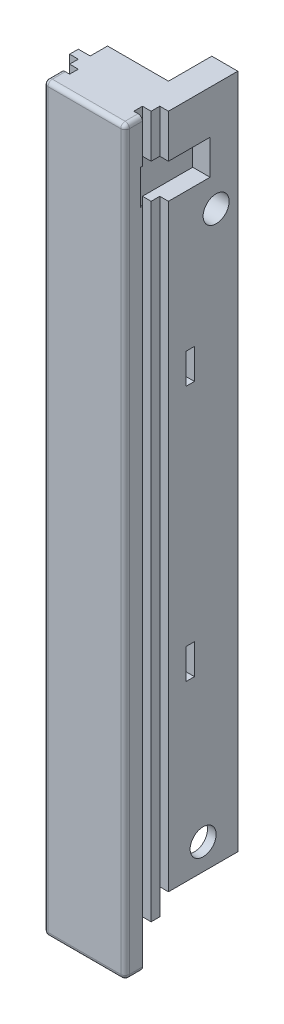
SolidWorks part; units mm, degrees
ref_plane "Front Plane" through (0, 0, 0) normal (0, 0, 1) x (1, 0, 0)
ref_plane "Top Plane" through (0, 0, 0) normal (0, 1, 0) x (1, 0, 0)
ref_plane "Right Plane" through (0, 0, 0) normal (1, 0, 0) x (0, 0, -1)
sketch "Sketch1" plane through (0, 0, 0) normal (0, 1, 0) x (1, 0, 0)
  line L0 (-3.4214, 1.8186) -> (-3.4214, 0.8186)
  line L1 (-4.4214, 3.8186) -> (4.9786, 3.8186)
  line L2 (-4.4214, 3.8186) -> (-4.4214, 1.8186)
  line L3 (-4.4214, 1.8186) -> (4.9786, 1.8186)
  line L4 (4.9786, 3.8186) -> (4.9786, 1.8186)
  line L5 (-3.4214, 0.8186) -> (-4.4214, 0.8186)
  line L6 (-4.4214, 0.8186) -> (-4.4214, -0.1814)
  line L7 (-4.4214, -0.1814) -> (4.9786, -0.1814)
  line L8 (4.9786, -0.1814) -> (4.9786, 0.8186)
  line L9 (4.9786, 0.8186) -> (3.9786, 0.8186)
  line L10 (3.9786, 0.8186) -> (3.9786, 1.8186)
  line L11 (4.9786, -0.1814) -> (5.9786, -0.1814)
  line L12 (5.9786, -0.1814) -> (5.9786, -8.1814)
  line L13 (5.9786, -8.1814) -> (2.9786, -8.1814)
  line L14 (2.9786, -8.1814) -> (2.9786, -3.1814)
  line L15 (2.9786, -3.1814) -> (-4.051, -3.1814)
  line L16 (-4.051, -3.1814) -> (-4.051, -1.1814)
  line L17 (-4.051, -1.1814) -> (-5.4214, -1.1814)
  line L18 (-5.4214, -1.1814) -> (-5.4214, -0.1814)
  line L19 (-5.4214, -0.1814) -> (-4.4214, -0.1814)
  dimension "D1" = 9.4
  dimension "D2" = 2
  dimension "D3" = 1
  dimension "D4" = 1
  dimension "D5" = 1
  dimension "D6" = 1
  dimension "D7" = 1
  dimension "D8" = 1
  dimension "D9" = 1
  dimension "D10" = 1
  dimension "D11" = 1
  dimension "D12" = 8
  dimension "D13" = 3
  dimension "D14" = 3
extrude "Boss-Extrude1" add sketch "Sketch1" against normal blind 85.5 contours L4 L1 L2 L3 region at (0.2786, 0, -2.8186)
extrude "Boss-Extrude2" add sketch "Sketch1<3>" against normal blind 81 contours L9 L10 L3 L0 L5 L6 L7 L8 region at (0.2786, 0, -0.7591)
sketch "Sketch1<3>" plane through (0, 0, 0) normal (0, 1, 0) x (1, 0, 0) same geometry as "Sketch1"
fillet "Fillet1" radius 0.5 8 edges at (-4.4214, -85.5, -2.8186) (4.9786, -85.5, -2.8186) (0.2786, -85.5, -3.8186) (-4.4214, 0, -2.8186) (4.9786, 0, -2.8186) (0.2786, 0, -3.8186) (4.9786, -42.75, -3.8186) (-4.4214, -42.75, -3.8186)
extrude "Boss-Extrude3" add sketch "Sketch1<4>" against normal blind 78 contours L19 L18 L17 L16 L15 L14 L13 L12 L11 L7 region at (1.9304, 0, 2.9434)
sketch "Sketch1<4>" plane through (0, 0, 0) normal (0, 1, 0) x (1, 0, 0) same geometry as "Sketch1"
sketch "Sketch2" plane through (5.9786, 0, 0) normal (1, 0, 0) x (0, 0, -1)
  line L0 (-0.1814, 0) -> (-8.1814, 0) construction
  line L1 (-0.1814, -78) -> (-8.1814, -78) construction
  line L3 (-0.1814, -78) -> (-0.1814, 0) construction
  line L4 (1.8186, -81) -> (1.8186, 0) construction
  line L5 (-4.9814, -5) -> (2.0186, -5)
  line L6 (-4.9814, -5) -> (-4.9814, -9)
  line L7 (-4.9814, -9) -> (2.0186, -9)
  line L8 (2.0186, -5) -> (2.0186, -9)
  circle A0 centre (-5.6814, -12.5) radius 1.5
  circle A1 centre (-4.1814, -75) radius 1.5
  line M6 (-0.1814, -78) -> (-0.1814, 0)
  dimension "D1" = 3
  dimension "D2" = 3
  dimension "D3" = 12.5
  dimension "D4" = 3
  dimension "D5" = 4
  dimension "D6" = 5.5
  dimension "D7" = 5
  dimension "D8" = 4
  dimension "D9" = 7
  dimension "D10" = 0.2
extrude "Cut-Extrude1" cut sketch "Sketch2" against normal through all contours A0 | A1 region at (5.9786, -12.5, 5.6814) region at (5.9786, -75, 4.1814)
extrude "Cut-Extrude2" cut sketch "Sketch2<3>" against normal up to surface (2 mm away) contours L6 L7 L5 M6 | L8 L5 L7 M6 region at (5.9786, -7, 2.5814) region at (5.9786, -7, -0.9186) up to face at (3.9786, -40.5, -1.3186)
sketch "Sketch2<3>" plane through (5.9786, 0, 0) normal (1, 0, 0) x (0, 0, -1) same geometry as "Sketch2"
sketch "Sketch3" plane through (0, 0, 8.1814) normal (0, 0, 1) x (1, 0, 0)
  line L0 (2.9786, -78) -> (2.9786, 0) construction
  line L1 (2.9786, -15) -> (4.9786, -15)
  line L2 (2.9786, -15) -> (2.9786, -78)
  line L3 (2.9786, -78) -> (4.9786, -78)
  line L4 (4.9786, -15) -> (4.9786, -78)
  line L6 (5.9786, -78) -> (2.9786, -78) construction
  line L7 (5.9786, 0) -> (2.9786, 0) construction
  line L8 (5.9786, -78) -> (5.9786, 0) construction
  dimension "D1" = 15
  dimension "D2" = 1
extrude "Cut-Extrude3" cut sketch "Sketch3" against normal up to surface (5 mm away) up to face at (-0.5362, -77.059, 3.1814)
sketch "Sketch4" plane through (5.9786, 0, 0) normal (1, 0, 0) x (0, 0, -1)
  line L0 (-0.1814, 0) -> (-8.1814, 0) construction
  line L1 (-2.1814, -28.5) -> (-3.1814, -28.5)
  line L2 (-2.1814, -28.5) -> (-2.1814, -25)
  line L3 (-2.1814, -25) -> (-3.1814, -25)
  line L4 (-3.1814, -28.5) -> (-3.1814, -25)
  line L5 (-2.1814, -58) -> (-3.1814, -58)
  line L6 (-2.1814, -58) -> (-2.1814, -54.5)
  line L7 (-2.1814, -54.5) -> (-3.1814, -54.5)
  line L8 (-3.1814, -58) -> (-3.1814, -54.5)
  line L9 (-0.1814, -78) -> (-0.1814, -9) construction
  line L10 (-0.1814, -78) -> (-0.1814, -9) construction
  line L11 (-0.1814, -78) -> (-8.1814, -78) construction
  point P8 (-2.6814, -25)
  dimension "D1" = 1
  dimension "D2" = 3.5
  dimension "D3" = 1
  dimension "D4" = 3.5
  dimension "D5" = 25
  dimension "D6" = 2
  dimension "D7" = 2
  dimension "D8" = 20
extrude "Cut-Extrude4" cut sketch "Sketch4" against normal blind 2
ref_plane "Plane1" through (0, 0, -13.8186) normal (0, 0, -1) x (-1, 0, 0)
mirror "Mirror1" about plane through (0, 0, -13.8186) normal (0, 0, -1) of bodies 107
delete or keep bodies "Body-Delete/Keep 1" type delete bodies bodies 107
